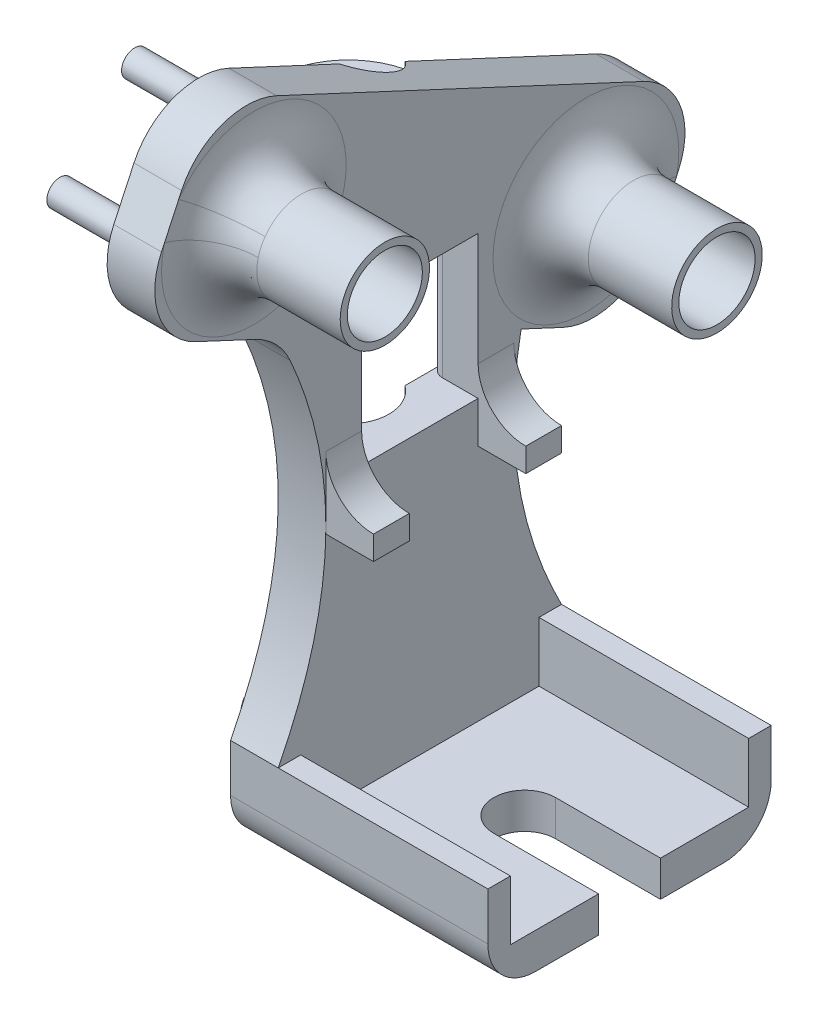
SolidWorks part; units mm, degrees
ref_plane "Front Plane" through (0, 0, 0) normal (0, 0, 1) x (1, 0, 0)
ref_plane "Top Plane" through (0, 0, 0) normal (0, 1, 0) x (1, 0, 0)
ref_plane "Right Plane" through (0, 0, 0) normal (1, 0, 0) x (0, 0, -1)
sketch "Sketch1" plane through (0, 0, 0) normal (1, 0, 0) x (0, 0, -1)
  line L0 (-17.7029, 8.255) -> (17.7029, -8.255) construction
  line L1 (0, 0) -> (17.7029, 0) construction
  line L2 (-22.1794, 21.5528) -> (-30.7671, 3.1366)
  line L3 (-30.7671, 3.1366) -> (22.1794, -21.5528)
  line L4 (22.1794, -21.5528) -> (30.7671, -3.1366)
  line L5 (30.7671, -3.1366) -> (-22.1794, 21.5528)
  line L6 (-17.7029, 8.255) -> (-26.4733, 12.3447) construction
  line L7 (22.1794, -21.5528) -> (-22.1794, 21.5528) construction
  line L8 (-30.7671, 3.1366) -> (30.7671, -3.1366) construction
  circle A0 centre (-17.7029, 8.255) radius 4 construction
  circle A1 centre (17.7029, -8.255) radius 4.064 construction
  circle A2 centre (-17.7029, 8.255) radius 4
  circle A3 centre (17.7029, -8.255) radius 4.064
  point P4 (0, 0)
  point P12 (0, 0)
  point P14 (-26.4733, 12.3447)
  dimension "D3" = 8
  dimension "D4" = 8.128
  dimension "D1" = 25
  dimension "D2" = 35.4058
  dimension "D5" = 58.42
  dimension "D6" = 20.32
extrude "Boss-Extrude1" add sketch "Sketch1" along normal blind 5.08
sketch "Sketch2" plane through (0, 0, 0) normal (-1, 0, 0) x (0, 0, 1)
  line L0 (15.1003, -4.1689) -> (15.1003, -53.975)
  line L1 (30.7671, 3.1366) -> (-22.1794, -21.5528) construction
  line L2 (15.1003, -53.975) -> (-15.1003, -53.975)
  line L3 (-15.1003, -53.975) -> (-15.1003, -18.2517)
  line L4 (17.7029, 8.255) -> (-17.7029, -8.255) construction
  line L5 (-15.1003, -18.2517) -> (15.1003, -4.1689)
  point P10 (0, -53.975)
  dimension "D1" = 30.2006
  dimension "D2" = 45.72
extrude "Boss-Extrude2" add sketch "Sketch2" against normal blind 5.08
sketch "Sketch4" plane through (5.08, 0, 0) normal (1, 0, 0) x (0, 0, -1)
  line L0 (15.1003, -18.2517) -> (15.1003, -53.975) construction
  line L1 (-15.1003, -53.975) -> (15.1003, -53.975)
  line L2 (-15.1003, -53.975) -> (-15.1003, -50.165)
  line L3 (-12.7, -50.165) -> (12.7, -50.165)
  line L4 (15.1003, -53.975) -> (15.1003, -59.309)
  line L5 (-12.7, -50.165) -> (-12.7, -43.815)
  line L6 (-12.7, -43.815) -> (-15.1003, -43.815)
  line L7 (-15.1003, -53.975) -> (-15.1003, -4.1689) construction
  line L8 (-15.1003, -43.815) -> (-15.1003, -50.165)
  line L9 (15.1003, -59.309) -> (15.1003, -43.815)
  line L10 (15.1003, -43.815) -> (12.7, -43.815)
  line L11 (12.7, -43.815) -> (12.7, -50.165)
  line M12 (-15.1003, -4.1689) -> (-15.1003, -53.975)
  line M13 (-15.1003, -53.975) -> (15.1003, -53.975)
  line M14 (15.1003, -53.975) -> (15.1003, -18.2517)
  dimension "D1" = 3.81
  dimension "D2" = 25.4
  dimension "D3" = 6.35
extrude "Boss-Extrude3" add sketch "Sketch4" along normal blind 22.352 contours L10 L11 L3 L5 L6 M12 M13 M14
sketch "Sketch5" plane through (0, -50.165, 0) normal (0, 1, 0) x (1, 0, 0)
  line L0 (16.256, 3.302) -> (27.432, 3.302)
  line L1 (27.432, 3.302) -> (27.432, -3.302)
  line L2 (27.432, -3.302) -> (16.256, -3.302)
  line L4 (5.08, 12.7) -> (5.08, -12.7)
  line L5 (5.08, -12.7) -> (27.432, -12.7)
  line L6 (27.432, -12.7) -> (27.432, 12.7)
  line L7 (27.432, 12.7) -> (5.08, 12.7)
  line L8 (5.08, 12.7) -> (5.08, -12.7) construction
  line L9 (5.08, -12.7) -> (27.432, -12.7) construction
  line L15 (27.432, -12.7) -> (27.432, 12.7) construction
  arc A0 (16.256, 3.302) -> (16.256, -3.302) centre (16.256, 0) ccw
  point P7 (16.256, -12.7)
  point P9 (27.432, 0)
  dimension "D2" = 6.604
  dimension "D1" = 0
extrude "Cut-Extrude1" cut sketch "Sketch5" against normal blind 22.352
sketch "Sketch6" plane through (5.08, 0, 0) normal (1, 0, 0) x (0, 0, -1)
  line L0 (-12.7, -50.165) -> (12.7, -50.165) construction
  line L1 (-10.0203, -22.225) -> (-6.2103, -22.225)
  line L2 (-10.0203, -22.225) -> (-10.0203, -24.765)
  line L3 (-10.0203, -24.765) -> (-6.2103, -24.765)
  line L4 (-6.2103, -22.225) -> (-6.2103, -24.765)
  line L5 (6.2103, -22.225) -> (10.0203, -22.225)
  line L6 (6.2103, -22.225) -> (6.2103, -24.765)
  line L7 (6.2103, -24.765) -> (10.0203, -24.765)
  line L8 (10.0203, -22.225) -> (10.0203, -24.765)
  line L9 (-15.1003, -43.815) -> (-15.1003, -4.1689) construction
  line L10 (-10.0203, -22.225) -> (-15.1003, -22.225) construction
  line L11 (10.0203, -22.225) -> (15.1003, -22.225) construction
  line L12 (15.1003, -18.2517) -> (15.1003, -43.815) construction
  dimension "D1" = 25.4
  dimension "D2" = 5.08
  dimension "D3" = 3.81
  dimension "D4" = 2.54
extrude "Boss-Extrude4" add sketch "Sketch6" along normal blind 5.08
sketch "Sketch7" plane through (0, -53.975, 0) normal (0, -1, 0) x (1, 0, 0)
  circle A0 centre (-2.54, 0) radius 4.318
  dimension "D1" = 8.636
  dimension "D2" = 2.54
extrude "Cut-Extrude2" cut sketch "Sketch7" against normal blind 72.644
sketch "Sketch8" plane through (0, -53.975, 0) normal (0, -1, 0) x (1, 0, 0)
  line L0 (0, 3.4919) -> (0, 15.1003) construction
  line L1 (0, -15.1003) -> (0, -3.4919) construction
  line L2 (0, 3.4919) -> (0, 7.7209)
  line L3 (0, -3.4919) -> (0, -7.7209)
  arc A0 (0, -3.4919) -> (0, 3.4919) centre (-2.54, 0) ccw construction
  arc A1 (0, -3.4919) -> (0, 3.4919) centre (-2.54, 0) ccw construction
  circle A2 centre (-2.54, 0) radius 4.318 construction
  arc A3 (0, 3.4919) -> (0, -3.4919) centre (-2.54, 0) ccw
  arc A4 (0, 7.7209) -> (0, -7.7209) centre (-2.54, 0) ccw
  dimension "D1" = 3.81
extrude "Boss-Extrude5" add sketch "Sketch8" against normal blind 3.81
ref_plane "Plane1" through (0, 4.445, 0) normal (0, -1, 0) x (-1, 0, 0)
sketch "Sketch9" plane through (0, 4.445, 0) normal (0, -1, 0) x (-1, 0, 0)
  line L2 (0, 7.7209) -> (0, 3.4919)
  line L3 (0, -3.4919) -> (0, -7.7209)
  line L4 (0, 7.7209) -> (0, 3.4919)
  line L5 (0, -3.4919) -> (0, -7.7209)
  arc A2 (0, -3.4919) -> (0, 3.4919) centre (2.54, 0) ccw
  arc A3 (0, -7.7209) -> (0, 7.7209) centre (2.54, 0) ccw
  arc A4 (0, -3.4919) -> (0, 3.4919) centre (2.54, 0) ccw
  arc A5 (0, -7.7209) -> (0, 7.7209) centre (2.54, 0) ccw
  dimension "D1" = 0
extrude "Boss-Extrude6" add sketch "Sketch9" along normal blind 3.81
fillet "Fillet2" radius 5.08 2 edges at (0, -50.165, -5.6064) (0, 0.635, -5.6064)
sketch "Sketch10" plane through (5.08, 0, 0) normal (1, 0, 0) x (0, 0, -1)
  line L0 (-15.1003, -43.815) -> (-15.1003, -4.1689) construction
  line L1 (-15.1003, -4.1689) -> (15.1003, -4.1689) construction
  line L2 (15.1003, -4.1689) -> (15.1003, -18.2517) construction
  line L3 (15.1003, -18.2517) -> (15.1003, -43.815) construction
  line L4 (-10.0203, -23.992) -> (-15.1003, -23.992) construction
  line L5 (10.0203, -23.992) -> (15.1003, -23.992) construction
  line L8 (15.1003, -18.2517) -> (15.1003, -43.815)
  line L9 (-15.1003, -4.1689) -> (-15.1003, -43.815)
  line L10 (15.1003, -18.2517) -> (10.7962, -16.2447)
  line L14 (-30.7671, 3.1366) -> (-15.1003, -4.1689) construction
  spline S0 degree 2 poles (-15.1003, -43.815) (-4.9403, -23.992) (-15.1003, -4.1689) knots 0 0 0 1 1 1
  spline S1 degree 3 poles (15.1003, -43.815) (10.39, -34.6249) (8.9554, -25.4348) (10.7962, -16.2447) knots 0 0 0 0 0.695411 0.695411 0.695411 0.695411
  point P5 (-15.1003, -23.992)
  dimension "D1" = 5.08
extrude "Cut-Extrude3" cut sketch "Sketch10" against normal up to surface (5.08 mm away) up to face at (0, -19.2899, -10.6665)
sketch "Sketch11" plane through (5.08, 0, 0) normal (1, 0, 0) x (0, 0, -1)
  circle A0 centre (-17.7029, 8.255) radius 4.762
  circle A1 centre (17.7029, -8.255) radius 4.826
  circle A2 centre (-17.7029, 8.255) radius 4 construction
  circle A3 centre (17.7029, -8.255) radius 4.064 construction
  circle A4 centre (17.7029, -8.255) radius 4.064
  circle A5 centre (-17.7029, 8.255) radius 4
  dimension "D1" = 0.762
  dimension "D2" = 0.762
extrude "Boss-Extrude7" add sketch "Sketch11" along normal blind 13.97
fillet "Fillet3" radius 5.08 2 edges at (5.08, -8.255, -22.5289) (5.08, 8.255, 12.9409)
fillet "Fillet1" radius 5.08 4 edges at (5.08, -22.225, -8.1153) (5.08, -22.225, 8.1153) (13.716, -53.975, -15.1003) (13.716, -53.975, 15.1003)
sketch "Sketch12" plane through (5.08, 0, 0) normal (1, 0, 0) x (0, 0, -1)
  line L0 (1.3208, -14.9352) -> (-1.3208, -14.9352) construction
  line L1 (-6.2103, -20.3543) -> (6.2103, -20.3543)
  line L2 (-6.2103, -20.3543) -> (-6.2103, -5.1143)
  line L3 (-6.2103, -5.1143) -> (6.2103, -5.1143)
  line L4 (6.2103, -20.3543) -> (6.2103, -5.1143)
  line L5 (1.3208, -14.9352) -> (-1.3208, -14.9352) construction
  line L6 (-10.287, -25.2984) -> (10.287, -25.2984) construction
  point P6 (0, -20.3543)
  point P7 (0, -14.9352)
  dimension "D1" = 4.9441
  dimension "D2" = 15.24
  dimension "D3" = 12.4206
extrude "Cut-Extrude4" cut sketch "Sketch12" against normal up to surface (21.8786 mm away)
fillet "Fillet4" radius 7.62 6 edges at (2.54, -4.1689, 15.1003) (2.54, -3.1366, -30.7671) (2.54, -21.5528, -22.1794) (2.54, 3.1366, 30.7671) (2.54, 21.5528, 22.1794)
sketch "Sketch15" plane through (0, 0, 0) normal (-1, 0, 0) x (0, 0, 1)
  circle A0 centre (17.7029, 8.255) radius 6.35
  dimension "D1" = 12.7
extrude "Cut-Extrude5" cut sketch "Sketch15" against normal blind 1.905
sketch "Sketch16" plane through (0, 0, 0) normal (-1, 0, 0) x (0, 0, 1)
  circle A0 centre (17.7029, 8.255) radius 12.065
  dimension "D1" = 24.13
extrude "Cut-Extrude6" cut sketch "Sketch16" along normal blind 9.525
sketch "Sketch14" plane through (0, 0, 0) normal (-1, 0, 0) x (0, 0, 1)
  circle A0 centre (17.7029, 16.2261) radius 1.397
  circle A1 centre (25.674, 8.255) radius 1.397
  circle A2 centre (17.7029, 0.284) radius 1.397
  dimension "D1" = 2.794
extrude "Boss-Extrude8" add sketch "Sketch14" along normal blind 7.62
fillet "Fillet5" radius 1.27 8 edges at (0, -49.53, -7.7209) (0, -49.53, 7.7209) (0, -1.4834, 7.7209) (0, 0, -7.7209) (-1.0611, -48.1922, 7.9923) (-1.0611, -1.3378, -7.9923) (0, -12.7343, -6.2103) (0, -12.7343, 6.2103)
